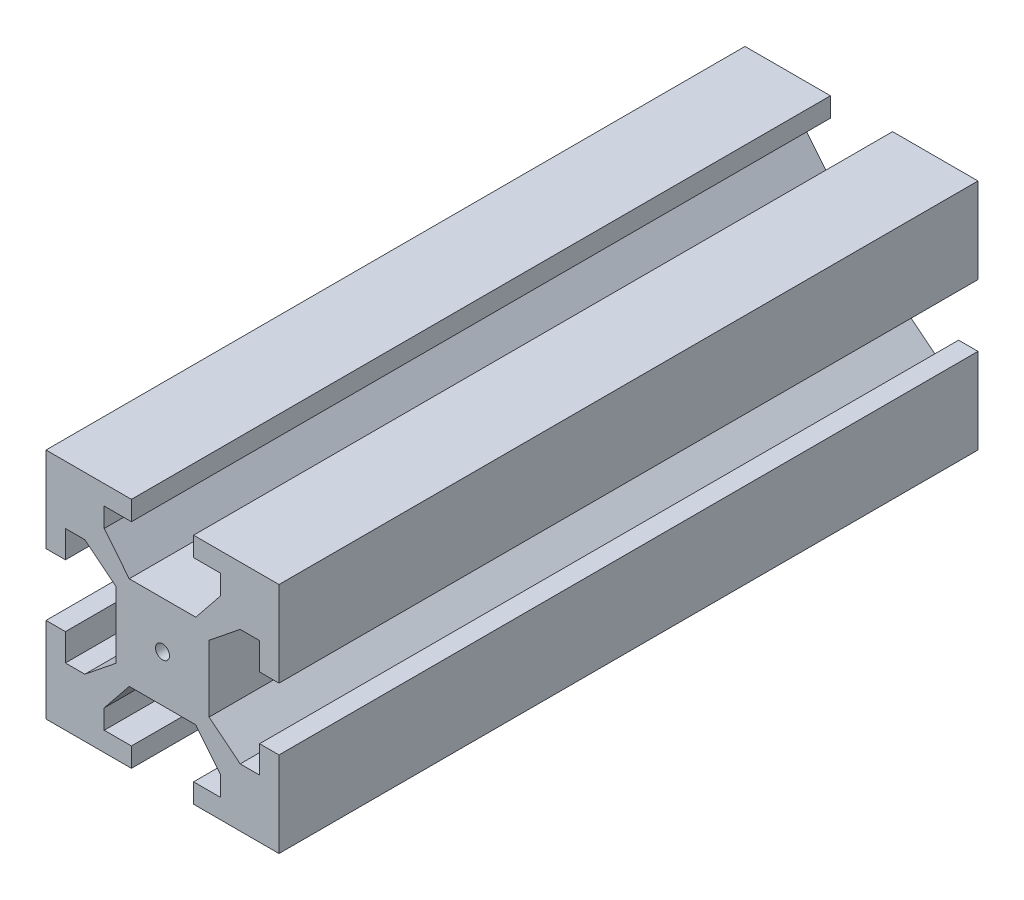
SolidWorks part; units mm, degrees
ref_plane "Front Plane" through (0, 0, 0) normal (0, 0, 1) x (1, 0, 0)
ref_plane "Top Plane" through (0, 0, 0) normal (0, 1, 0) x (1, 0, 0)
ref_plane "Right Plane" through (0, 0, 0) normal (1, 0, 0) x (0, 0, -1)
sketch "Sketch1" plane through (0, 0, 0) normal (0, 0, 1) x (1, 0, 0)
  line L1 (25, 25) -> (6.6667, 25)
  line L2 (25, 25) -> (25, 6.6667)
  line L3 (25, -25) -> (6.6667, -25)
  line L4 (-25, 25) -> (-25, 6.6667)
  line L6 (20.8333, -6.6667) -> (25, -6.6667)
  line L7 (25, 0) -> (10, 0) construction
  line L8 (25, -6.6667) -> (25, -25)
  line L9 (25, 6.6667) -> (25, 0) construction
  line L10 (25, 0) -> (25, -6.6667) construction
  line L11 (20.8333, -6.6667) -> (20.8333, -12.5)
  line L12 (20.8333, -12.5) -> (16.6667, -12.5)
  line L13 (16.6667, -12.5) -> (10, -7.1429)
  line L14 (10, -7.1429) -> (10, 7.1429)
  line L16 (12.5, -16.6667) -> (7.1429, -10)
  line L17 (20.8333, 6.6667) -> (25, 6.6667)
  line L18 (20.8333, 6.6667) -> (20.8333, 12.5)
  line L19 (20.8333, 12.5) -> (16.6667, 12.5)
  line L20 (16.6667, 12.5) -> (10, 7.1429)
  line L21 (-25, 0) -> (25, 0) construction
  line L22 (-7.1429, -10) -> (7.1429, -10)
  line L23 (-12.5, -16.6667) -> (-7.1429, -10)
  line L24 (-12.5, -20.8333) -> (-12.5, -16.6667)
  line L25 (-6.6667, -20.8333) -> (-12.5, -20.8333)
  line L26 (-6.6667, -20.8333) -> (-6.6667, -25)
  line L27 (6.6667, -20.8333) -> (6.6667, -25)
  line L28 (6.6667, -20.8333) -> (12.5, -20.8333)
  line L29 (12.5, -20.8333) -> (12.5, -16.6667)
  line L30 (-16.6667, -12.5) -> (-10, -7.1429)
  line L31 (-10, 7.1429) -> (-10, -7.1429)
  line L32 (-16.6667, 12.5) -> (-10, 7.1429)
  line L33 (-20.8333, 12.5) -> (-16.6667, 12.5)
  line L34 (-20.8333, 6.6667) -> (-20.8333, 12.5)
  line L35 (-20.8333, 6.6667) -> (-25, 6.6667)
  line L36 (-20.8333, -6.6667) -> (-25, -6.6667)
  line L37 (-20.8333, -6.6667) -> (-20.8333, -12.5)
  line L38 (-20.8333, -12.5) -> (-16.6667, -12.5)
  line L39 (-12.5, 16.6667) -> (-7.1429, 10)
  line L40 (7.1429, 10) -> (-7.1429, 10)
  line L41 (12.5, 16.6667) -> (7.1429, 10)
  line L42 (12.5, 20.8333) -> (12.5, 16.6667)
  line L43 (6.6667, 20.8333) -> (12.5, 20.8333)
  line L44 (6.6667, 20.8333) -> (6.6667, 25)
  line L45 (-6.6667, 20.8333) -> (-6.6667, 25)
  line L46 (-6.6667, 20.8333) -> (-12.5, 20.8333)
  line L47 (-12.5, 20.8333) -> (-12.5, 16.6667)
  line L48 (-6.6667, 25) -> (-25, 25)
  line L49 (6.6667, 25) -> (-6.6667, 25) construction
  line L50 (-25, -6.6667) -> (-25, -25)
  line L51 (-25, 6.6667) -> (-25, 0) construction
  line L52 (-25, 0) -> (-25, -6.6667) construction
  line L53 (-6.6667, -25) -> (-25, -25)
  line L54 (6.6667, -25) -> (-6.6667, -25) construction
  circle A0 centre (0, 0) radius 1.5
  point P6 (0, 0)
  point P54 (-10, 0)
  dimension "D7" = 3
  dimension "D2" = 50
  dimension "D1" = 13.3333
  dimension "D3" = 4.1667
  dimension "D4" = 15
  dimension "D5" = 7.1429
  dimension "D6" = 12.5
  dimension "D9" = 4
extrude "Boss-Extrude1" add sketch "Sketch1" along normal mid plane 150
ref_axis "Axis1" through (0, 0, -101.6417) along (0, 0, 1)
equation "\"var1\"=50"
equation "\"D2@Sketch1\"=\"var1\""
equation "\"D1@Sketch1\"=\"var1\"/3.75"
equation "\"D3@Sketch1\"=\"var1\"/12"
equation "\"D4@Sketch1\"=\"var1\"*0.3"
equation "\"D5@Sketch1\"=\"var1\"/7"
equation "\"D6@Sketch1\"=\"var1\"/4"
